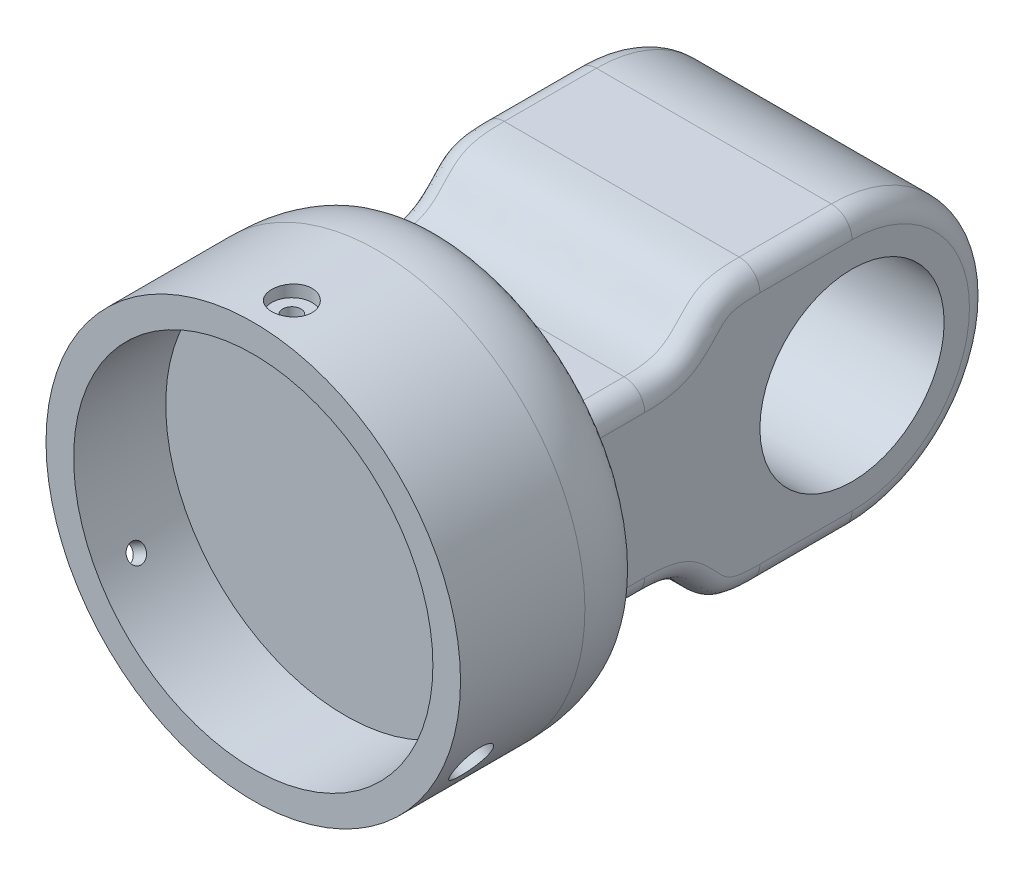
SolidWorks part; units mm, degrees
material "AISI 1020"
ref_plane "Front Plane" through (0, 0, 0) normal (0, 0, 1) x (1, 0, 0)
ref_plane "Top Plane" through (0, 0, 0) normal (0, 1, 0) x (1, 0, 0)
ref_plane "Right Plane" through (0, 0, 0) normal (1, 0, 0) x (0, 0, -1)
sketch "Sketch1" plane through (0, 0, 0) normal (0, 0, 1) x (1, 0, 0)
  circle A0 centre (0, 0) radius 114.3
  dimension "D1" = 228.6
extrude "Boss-Extrude1" add sketch "Sketch1" along normal blind 101.6
sketch "Sketch3" plane through (0, 0, 101.6) normal (0, 0, 1) x (1, 0, 0)
  circle A0 centre (0, 0) radius 99.06
  circle A1 centre (0, 0) radius 114.3 construction
  dimension "D1" = 15.24
extrude "Cut-Extrude1" cut sketch "Sketch3" against normal blind 50.8
sketch "Sketch4" plane through (0, 0, 0) normal (1, 0, 0) x (0, 0, -1)
  line L0 (0, -50.8) -> (38.1, -50.8)
  line L1 (101.6, -76.2) -> (152.4, -76.2)
  line L3 (101.6, 76.2) -> (152.4, 76.2)
  line L5 (0, -114.3) -> (0, 114.3) construction
  line L7 (0, 50.8) -> (0, -50.8)
  line L9 (0, 50.8) -> (38.1, 50.8)
  line L10 (0, 0) -> (38.1, 50.8) construction
  line L11 (38.1, -50.8) -> (0, 0) construction
  line L12 (125.73, 0) -> (-125.73, 0) construction
  arc A0 (152.4, 76.2) -> (152.4, -76.2) centre (152.4, 0) cw
  circle A1 centre (152.4, 0) radius 50.8
  spline S0 degree 3 poles (38.1, 50.8) (49.4593, 50.8) (60.7562, 53.4009) (76.5747, 74.0503) (88.0739, 76.2) (101.6, 76.2) knots 0 0 0 0 0.363391 0.590697 1 1 1 1
  spline S1 degree 3 poles (38.1, -50.8) (49.4593, -50.8) (60.7562, -53.4009) (76.5747, -74.0503) (88.0739, -76.2) (101.6, -76.2) knots 0 0 0 0 0.363391 0.590697 1 1 1 1
  point P5 (62.6196, 57.632)
  point P8 (0, 0)
  point P11 (0, 0)
  point P18 (73.8779, 68.8903)
  dimension "D1" = 101.6
  dimension "D3" = 101.6
  dimension "D2" = 76.2
  dimension "D7" = 62.6196
  dimension "D4" = 152.4
  dimension "D5" = 38.1
  dimension "D6" = 50.8
  dimension "D8" = 73.8779
extrude "Boss-Extrude2" add sketch "Sketch4" along normal blind 76.2 and the other way blind 76.2
hole_wizard "CBORE for 3/8 Hex Head Bolt2" positions "3DSketch3" profile "Sketch8" counterbore size "3/8" standard "ANSI Inch" end condition up to next
sketch3d "3DSketch3"
  line L0 (0, 0, 0) -> (0, 0, 160.6437) construction
  line L1 (-76.2, 76.2, 0) -> (76.2, 76.2, 0) construction
  point P0 (0, 114.3, 80.3219)
  point P8 (0.3033, 114.2996, 34.6949)
  point P9 (0, 0, 0)
  point P10 (9.0972, 113.9374, 46.8262)
  point P14 (0, 0, 0)
  point P15 (0, 0, 80.3219)
  dimension "D1" = 88.9
sketch "Sketch8" plane through (0, 114.3, 80.3219) normal (1, 0, 0) x (0, 0, 1)
  line L0 (0, 0) -> (0, 15.24)
  line L1 (0, 15.24) -> (5.0419, 15.24)
  line L3 (5.0419, 15.24) -> (5.0419, 6.8072)
  line L4 (5.0419, 6.8072) -> (11.1125, 6.8072)
  line L5 (11.1125, 6.8072) -> (11.1125, 0)
  line L7 (11.1125, 0) -> (0, 0)
  line L11 (0, -6.35) -> (0, 107.95) construction
  dimension "Thru Hole Dia." = 10.0838
  dimension "Thru Hole Depth" = 15.24
  dimension "C'Bore Dia." = 22.225
  dimension "C'Bore Depth" = 6.8072
pattern_circular "CirPattern1" count 3 every 120 about axis through (0, 0, 101.6) along (0, 0, 1) of "CBORE for 3/8 Hex Head Bolt2"
fillet "Fillet2" radius 11.43 1 edges at (114.3, 0, 0) second distance 33.02 first distance on face at (0, 0, 0)
fillet "Fillet3" radius 11.43 14 edges at (-76.2, -76.2, -127) (-76.2, 0, -228.6) (76.2, -76.2, -127) (76.2, 0, -228.6) (-76.2, 76.2, -127) (76.2, 76.2, -127) (-76.2, -50.8, -19.05) (-76.2, 50.8, -19.05) (76.2, -50.8, -19.05) (76.2, 50.8, -19.05)
fillet "Fillet4" radius 8.89 8 edges at (72.8522, 47.4522, 0) (0, 50.8, 0) (-72.8522, 47.4522, 0) (-76.2, 0, 0) (-72.8522, -47.4522, 0) (0, -50.8, 0) (72.8522, -47.4522, 0) (76.2, 0, 0)
